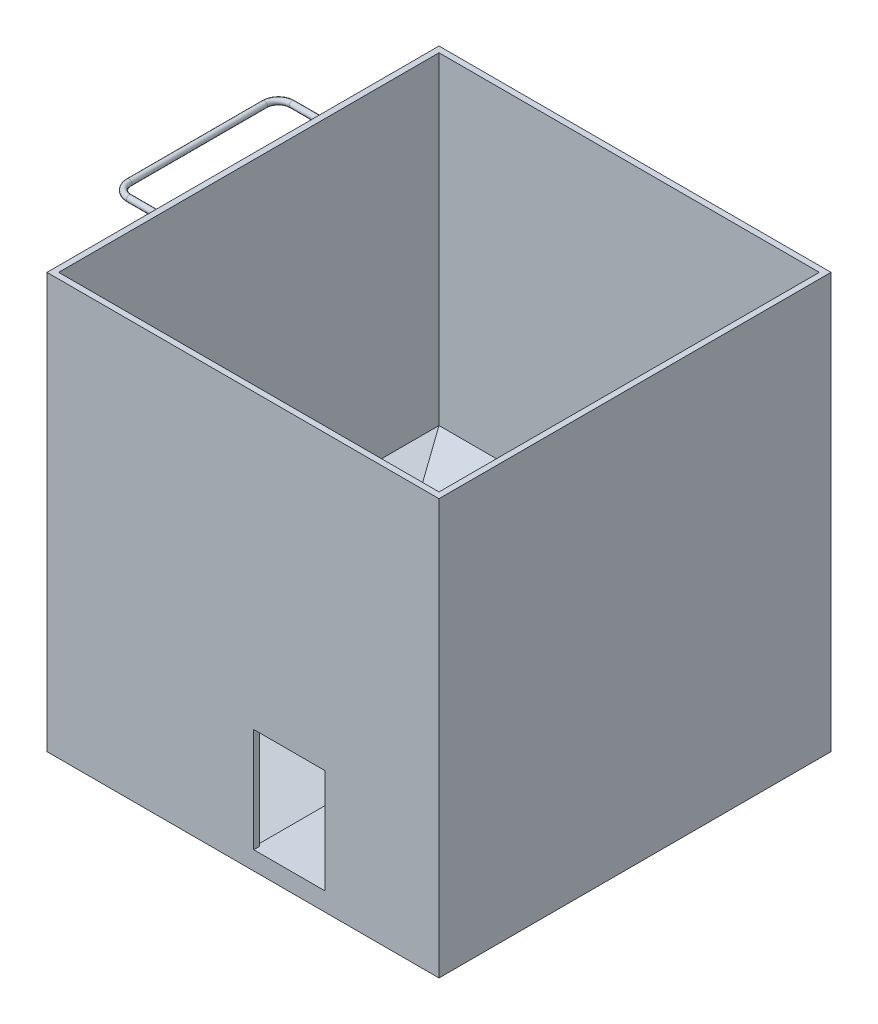
SolidWorks part; units mm, degrees
ref_plane "Front" through (0, 0, 0) normal (0, 0, 1) x (1, 0, 0)
ref_plane "Top" through (0, 0, 0) normal (0, 1, 0) x (1, 0, 0)
ref_plane "Right" through (0, 0, 0) normal (1, 0, 0) x (0, 0, -1)
sketch "Croquis1" plane through (0, 0, 0) normal (0, 1, 0) x (1, 0, 0)
  line L1 (0, 0) -> (850, 0)
  line L2 (0, 0) -> (0, 850)
  line L3 (0, 850) -> (850, 850)
  line L4 (850, 0) -> (850, 850)
  dimension "D1" = 850
  dimension "D2" = 850
extrude "Saliente-Extruir1" add sketch "Croquis1" along normal blind 700
shell "Vaciado1" thickness 12.7 removed face at (425, 700, -425) removed face at (425, 0, -425)
sketch "Croquis2" plane through (0, 0, 0) normal (0, -1, 0) x (1, 0, 0)
  line L1 (0, -850) -> (850, -850)
  line L2 (0, -850) -> (0, 0)
  line L3 (0, 0) -> (850, 0)
  line L4 (850, -850) -> (850, 0)
extrude "Saliente-Extruir2" add sketch "Croquis2" along normal blind 200
sketch "Croquis3" plane through (0, -200, 0) normal (0, -1, 0) x (1, 0, 0)
  line L0 (425, 0) -> (425, -850) construction
  line L1 (850, 0) -> (0, 0) construction
  line L2 (0, -850) -> (850, -850) construction
  line L3 (0, -425) -> (850, -425) construction
  line L4 (0, 0) -> (0, -850) construction
  line L5 (850, -850) -> (850, 0) construction
  line L6 (229.4049, -55.6114) -> (229.4049, -105.6114)
  line L7 (770.5951, -55.6114) -> (620.5951, -55.6114)
  line L8 (770.5951, -55.6114) -> (770.5951, -105.6114)
  line L9 (770.5951, -105.6114) -> (620.5951, -105.6114)
  line L10 (620.5951, -55.6114) -> (620.5951, -105.6114)
  line L11 (79.4049, -105.6114) -> (229.4049, -105.6114)
  line L12 (79.4049, -55.6114) -> (79.4049, -105.6114)
  line L13 (79.4049, -55.6114) -> (229.4049, -55.6114)
  line L14 (79.4049, -794.3886) -> (229.4049, -794.3886)
  line L15 (79.4049, -794.3886) -> (79.4049, -744.3886)
  line L16 (79.4049, -744.3886) -> (229.4049, -744.3886)
  line L17 (620.5951, -794.3886) -> (620.5951, -744.3886)
  line L18 (770.5951, -744.3886) -> (620.5951, -744.3886)
  line L19 (770.5951, -794.3886) -> (770.5951, -744.3886)
  line L20 (770.5951, -794.3886) -> (620.5951, -794.3886)
  line L21 (229.4049, -794.3886) -> (229.4049, -744.3886)
  dimension "D1" = 150
  dimension "D2" = 50
extrude "Cortar-Extruir1" cut sketch "Croquis3" against normal blind 90
ref_plane "Plano1" through (0, 680, 0) normal (0, 1, 0) x (1, 0, 0)
ref_plane "Plano2" through (0, -160, 0) normal (0, -1, 0) x (-1, 0, 0)
sketch "Croquis6" plane through (0, -160, 0) normal (0, -1, 0) x (-1, 0, 0)
  line L5 (-12.7, 12.7) -> (-837.3, 12.7) construction
  line L6 (-602.7651, 12.7) -> (-442.7651, 12.7)
  line L7 (-602.7651, 12.7) -> (-602.7651, 172.7)
  line L8 (-602.7651, 172.7) -> (-442.7651, 172.7)
  line L9 (-442.7651, 12.7) -> (-442.7651, 172.7)
  dimension "D1" = 160
  dimension "D2" = 160
sketch "Croquis8" plane through (0, 0, 0) normal (0, 1, 0) x (1, 0, 0)
  line L1 (12.7, 12.7) -> (837.3, 12.7)
  line L2 (12.7, 12.7) -> (12.7, 837.3)
  line L3 (12.7, 837.3) -> (837.3, 837.3)
  line L4 (837.3, 12.7) -> (837.3, 837.3)
loft "Cortar-Recubrir1" cut profiles "Croquis8", "Croquis6" connector at (12.7, 0, -12.7) connector at (442.7651, -160, -12.7)
sketch "Croquis9" plane through (837.3, 0, 0) normal (-1, 0, 0) x (0, 0, 1)
  line L6 (-507.3763, -153.7031) -> (-714.233, -153.7031)
  line L7 (-507.3763, -153.7031) -> (-507.3763, -56.1761)
  line L8 (-507.3763, -56.1761) -> (-714.233, -56.1761)
  line L9 (-714.233, -153.7031) -> (-714.233, -56.1761)
sketch "Croquis10" plane through (0, 0, 0) normal (-1, 0, 0) x (0, 0, 1)
  line L0 (-425, -200) -> (-425, 700) construction
  line L1 (0, -200) -> (-850, -200) construction
  line L2 (-850, 700) -> (0, 700) construction
  circle A0 centre (-248.2987, 680) radius 12.7
  circle A1 centre (-601.7013, 680) radius 12.7
  dimension "D1" = 25.4
  dimension "D2" = 20
sketch "Croquis11" plane through (0, 680, 0) normal (0, 1, 0) x (1, 0, 0)
  line L1 (0, 248.2987) -> (-70, 248.2987)
  line L3 (0, 601.7013) -> (-70, 601.7013)
  line L4 (-100, 278.2987) -> (-100, 571.7013)
  arc A0 (-100, 571.7013) -> (-70, 601.7013) centre (-70, 571.7013) cw
  arc A1 (-100, 278.2987) -> (-70, 248.2987) centre (-70, 278.2987) ccw
  point P9 (-100, 248.2987)
  dimension "D2" = 30
  dimension "D1" = 100
sweep "Barrer4" add path "Croquis11" circular profile diameter 12.7 parameters "D3"=12.7
sketch "Croquis28" plane through (0, 0, -12.7) normal (0, 0, -1) x (-1, 0, 0)
  line L1 (-602.7651, -160) -> (-448.3432, -160)
  line L2 (-602.7651, -160) -> (-602.7651, 65.8054)
  line L3 (-602.7651, 65.8054) -> (-448.3432, 65.8054)
  line L4 (-448.3432, -160) -> (-448.3432, 65.8054)
extrude "Cortar-Extruir2" cut sketch "Croquis28" against normal up to next
sketch "Croquis29" plane through (850, 0, 0) normal (1, 0, 0) x (0, 0, -1)
  line L0 (384.9486, 352.4136) -> (529.6152, 352.4136) construction
  line L4 (350.48, 485.0409) -> (495.1467, 485.0409) construction
